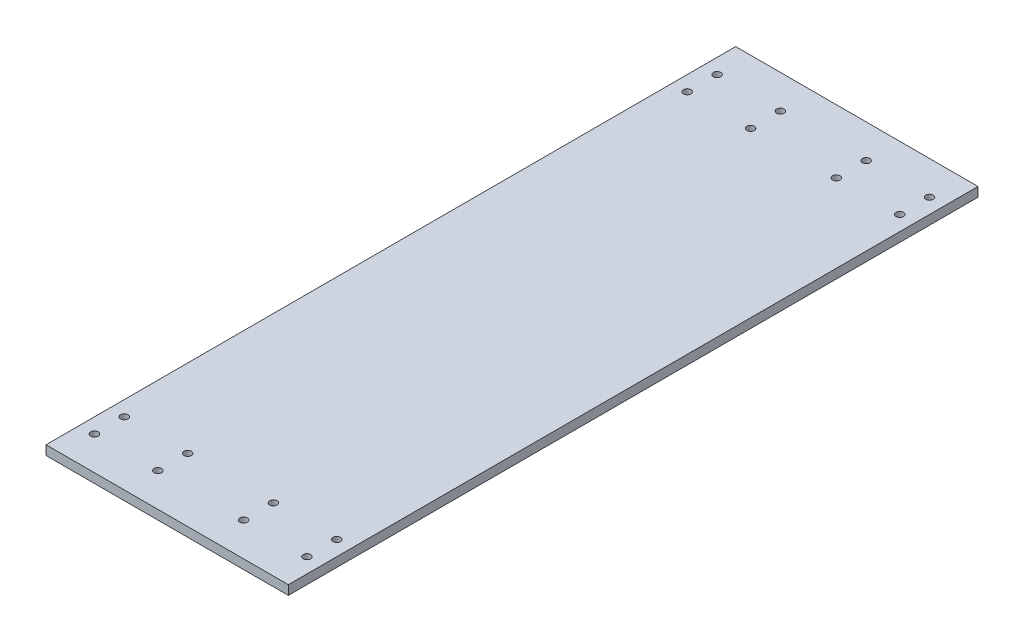
SolidWorks part; units mm, degrees
ref_plane "Front Plane" through (0, 0, 0) normal (0, 0, 1) x (1, 0, 0)
ref_plane "Top Plane" through (0, 0, 0) normal (0, 1, 0) x (1, 0, 0)
ref_plane "Right Plane" through (0, 0, 0) normal (1, 0, 0) x (0, 0, -1)
sketch "Sketch2" plane through (0, 0, 0) normal (0, 1, 0) x (1, 0, 0)
  line L1 (-65, -185) -> (65, -185)
  line L2 (-65, -185) -> (-65, 185)
  line L3 (-65, 185) -> (65, 185)
  line L4 (65, -185) -> (65, 185)
  line L5 (-65, -185) -> (65, 185) construction
  line L6 (-65, 185) -> (65, -185) construction
  point P0 (0, 0)
  dimension "D1" = 370
  dimension "D2" = 130
extrude "Boss-Extrude1" add sketch "Sketch2" along normal blind 5
sketch "Sketch3" plane through (0, 5, 0) normal (0, 1, 0) x (1, 0, 0)
  line L0 (-65, 185) -> (-65, -185) construction
  line L1 (65, 185) -> (-65, 185) construction
  circle A0 centre (-57, 167) radius 2
  circle A1 centre (-57, 151) radius 2
  circle A2 centre (-23, 167) radius 2
  circle A3 centre (-23, 151) radius 2
  dimension "D1" = 4
  dimension "D2" = 4
  dimension "D3" = 4
  dimension "D4" = 4
  dimension "D5" = 8
  dimension "D6" = 34
  dimension "D7" = 18
  dimension "D8" = 16
extrude "Cut-Extrude1" cut sketch "Sketch3" against normal blind 10
mirror "Mirror1" about plane through (0, 0, 0) normal (0, 0, 1) of "Cut-Extrude1" second plane through (0, 0, 0) second plane normal (1, 0, 0)
